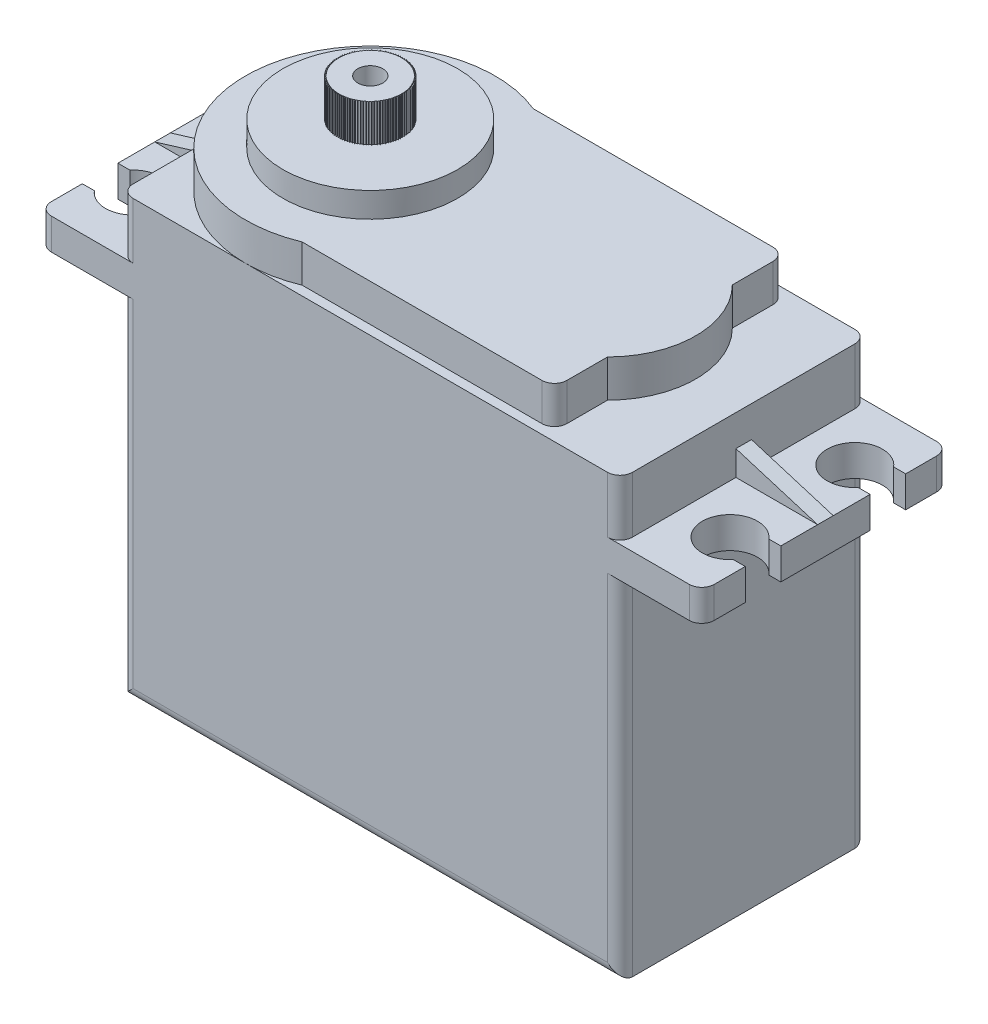
SolidWorks part; units mm, degrees
ref_plane "Front" through (0, 0, 0) normal (0, 0, 1) x (1, 0, 0)
ref_plane "Top" through (0, 0, 0) normal (0, 1, 0) x (1, 0, 0)
ref_plane "Right" through (0, 0, 0) normal (1, 0, 0) x (0, 0, -1)
sketch "Sketch1" plane through (0, 0, 0) normal (0, 1, 0) x (1, 0, 0)
  line L1 (0, 0) -> (40, 0)
  line L2 (0, 0) -> (0, 19.82)
  line L3 (0, 19.82) -> (40, 19.82)
  line L4 (40, 0) -> (40, 19.82)
  dimension "D1" = 40
  dimension "D2" = 19.82
extrude "Boss-Extrude1" add sketch "Sketch1" along normal blind 35
sketch "Sketch2" plane through (40, 0, 0) normal (1, 0, 0) x (0, 0, -1)
  line L0 (0, 28) -> (0, 30.5)
  line L1 (0, 0) -> (19.82, 0) construction
  line L2 (0, 30.5) -> (19.82, 30.5)
  line L3 (0, 35) -> (0, 0) construction
  line L4 (19.82, 35) -> (19.82, 0) construction
  line L5 (19.82, 30.5) -> (19.82, 28)
  line L6 (19.82, 28) -> (0, 28)
  dimension "D1" = 28
  dimension "D2" = 2.5
extrude "Boss-Extrude2" add sketch "Sketch2" along normal blind 6.55 and the other way blind 46.55
sketch "Sketch4" plane through (0, 30.5, 0) normal (0, 1, 0) x (1, 0, 0)
  line L0 (20, 19.82) -> (20, 0) construction
  line L1 (40, 19.82) -> (0, 19.82) construction
  line L2 (43.9, 14.91) -> (47.7926, 14.91) construction
  line L3 (0, 0) -> (40, 0) construction
  line L4 (20, 9.91) -> (-6.55, 9.91) construction
  line L5 (-6.55, 19.82) -> (-6.55, 0) construction
  line L6 (-3.9, 4.91) -> (-3.9, 14.91) construction
  line L7 (-3.9, 14.91) -> (-7.7926, 14.91) construction
  line L8 (-6.55, 16.335) -> (-6.55, 13.485)
  line L9 (40, 0) -> (40, 19.82) construction
  line L10 (-6.55, 3.485) -> (-5.5892, 3.485)
  line L11 (-6.55, 3.485) -> (-6.55, 6.335)
  line L12 (-6.55, 16.335) -> (-5.5892, 16.335)
  line L13 (-6.55, 13.485) -> (-5.5892, 13.485)
  line L14 (-6.55, 6.335) -> (-5.5892, 6.335)
  line L15 (43.9, 4.91) -> (43.9, 14.91) construction
  line L16 (46.55, 6.335) -> (45.5892, 6.335)
  line L17 (46.55, 13.485) -> (45.5892, 13.485)
  line L18 (46.55, 16.335) -> (45.5892, 16.335)
  line L19 (46.55, 3.485) -> (46.55, 6.335)
  line L20 (46.55, 3.485) -> (45.5892, 3.485)
  line L21 (46.55, 16.335) -> (46.55, 13.485)
  arc A0 (-5.5892, 3.485) -> (-5.5892, 6.335) centre (-3.9, 4.91) ccw
  arc A1 (45.5892, 16.335) -> (45.5892, 13.485) centre (43.9, 14.91) ccw
  arc A2 (45.5892, 3.485) -> (45.5892, 6.335) centre (43.9, 4.91) cw
  arc A3 (-5.5892, 16.335) -> (-5.5892, 13.485) centre (-3.9, 14.91) cw
  dimension "D1" = 43.9
  dimension "D5" = 0.9608
  dimension "D3" = 5
  dimension "D7" = 2.21
  dimension "D6" = 0.9608
extrude "Cut-Extrude1" cut sketch "Sketch4" against normal up to surface (2.5 mm away) up to face at (43.275, 28, -9.91)
sketch "Sketch5" plane through (0, 30.5, 0) normal (0, 1, 0) x (1, 0, 0)
  line L0 (46.55, 10.535) -> (40, 10.535)
  line L1 (-6.55, 10.535) -> (-6.55, 9.285)
  line L3 (0, 19.82) -> (0, 0) construction
  line L4 (40, 10.535) -> (40, 9.285)
  line L6 (40, 9.285) -> (46.55, 9.285)
  line L7 (46.55, 10.535) -> (46.55, 9.285)
  line L8 (-6.55, 13.485) -> (-6.55, 6.335) construction
  line L9 (0, 9.285) -> (-6.55, 9.285)
  line L10 (0, 10.535) -> (0, 9.285)
  line L11 (-6.55, 10.535) -> (0, 10.535)
  line L12 (20, 19.82) -> (20, 0) construction
  line L13 (40, 19.82) -> (0, 19.82) construction
  line L14 (0, 0) -> (40, 0) construction
  line L15 (20, 9.91) -> (-10.1525, 9.91) construction
  dimension "D1" = 1.25
  dimension "D2" = 0.625
extrude "Boss-Extrude3" add sketch "Sketch5" along normal blind 2
sketch "Sketch6" plane through (0, 0, -9.285) normal (0, 0, 1) x (1, 0, 0)
  line L0 (40, 32.5) -> (46.55, 30.5)
  line L1 (-6.55, 30.5) -> (0, 32.5)
  line L3 (40, 32.5) -> (46.55, 32.5)
  line L4 (46.55, 32.5) -> (46.55, 30.5)
  line L5 (0, 32.5) -> (-6.55, 32.5)
  line L6 (-6.55, 32.5) -> (-6.55, 30.5)
  line L7 (-6.55, 32.5) -> (0, 32.5) construction
extrude "Cut-Extrude2" cut sketch "Sketch6" against normal through all
sketch "Sketch8" plane through (0, 35, 0) normal (0, 1, 0) x (1, 0, 0)
  line L0 (34, 15) -> (34, 19.25)
  line L2 (34, 0.75) -> (13.7997, 0.75)
  line L4 (34, 0.75) -> (34, 5)
  line L6 (34, 19.25) -> (13.7997, 19.25)
  arc A0 (13.7997, 19.25) -> (13.7997, 0.75) centre (10, 10) ccw
  arc A1 (34, 15) -> (34, 5) centre (29, 10) cw
extrude "Boss-Extrude4" add sketch "Sketch8" along normal blind 3
sketch "Sketch9" plane through (0, 38, 0) normal (0, 1, 0) x (1, 0, 0)
  circle A0 centre (10, 10) radius 7
extrude "Boss-Extrude5" add sketch "Sketch9" along normal blind 2
sketch "Sketch10" plane through (0, 40, 0) normal (0, 1, 0) x (1, 0, 0)
  circle A0 centre (10, 10) radius 2.5
extrude "Boss-Extrude6" add sketch "Sketch10" along normal blind 3
sketch "Sketch11" plane through (0, 43, 0) normal (0, 1, 0) x (1, 0, 0)
  line L1 (10, 12.6) -> (10.0147, 12.5)
  line L2 (10, 12.6) -> (9.9853, 12.5)
  circle A1 centre (10, 10) radius 2.5 construction
  arc A2 (10.0147, 12.5) -> (9.9853, 12.5) centre (10, 10) ccw
extrude "Boss-Extrude7" add sketch "Sketch11" against normal up to surface (3 mm away) up to face at (10, 40, -3)
pattern_circular "CirPattern2" count 100 over 360 about axis through (10, 43, -10) along (0, -1, 0) of "Boss-Extrude7"
sketch "Sketch12" plane through (0, 43, 0) normal (0, 1, 0) x (1, 0, 0)
  circle A0 centre (10, 10) radius 1
extrude "Cut-Extrude3" cut sketch "Sketch12" against normal up to surface (8 mm away) up to face at (2.643, 35, -2.643)
fillet "Fillet1" radius 1 16 edges at (20, 0, -19.82) (20, 0, 0) (0, 32.75, 0) (34, 36.5, -19.25) (34, 36.5, -0.75) (40, 14, -19.82) (46.55, 29.25, -19.82) (40, 32.75, -19.82) (0, 14, -19.82) (-6.55, 29.25, -19.82) (0, 32.75, -19.82) (46.55, 29.25, 0) (40, 32.75, 0) (40, 14, 0) (-6.55, 29.25, 0) (0, 14, 0)
